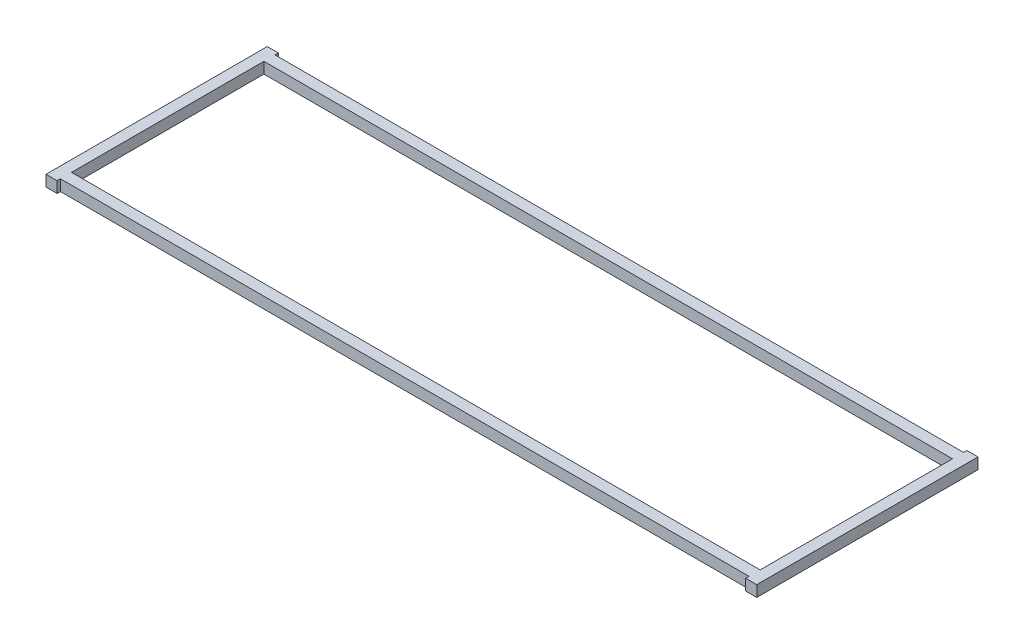
SolidWorks part; units mm, degrees
ref_plane "Front" through (0, 0, 0) normal (0, 0, 1) x (1, 0, 0)
ref_plane "Top" through (0, 0, 0) normal (0, 1, 0) x (1, 0, 0)
ref_plane "Right" through (0, 0, 0) normal (1, 0, 0) x (0, 0, -1)
sketch "Sketch1" plane through (0, 0, 0) normal (0, 1, 0) x (1, 0, 0)
  line L0 (196.85, 63.2524) -> (203.2, 63.2524)
  line L1 (-203.2, 63.2524) -> (-196.85, 63.2524)
  line L2 (-203.2, 63.2524) -> (-203.2, -63.2524)
  line L3 (-203.2, -63.2524) -> (-196.85, -63.2524)
  line L4 (203.2, 63.2524) -> (203.2, -63.2524)
  line L5 (-203.2, 63.2524) -> (203.2, -63.2524) construction
  line L6 (-203.2, -63.2524) -> (203.2, 63.2524) construction
  line L8 (-196.85, 63.2524) -> (-196.85, 61.3442)
  line L9 (-196.85, 61.3442) -> (196.85, 61.3442)
  line L10 (196.85, 63.2524) -> (196.85, 61.3442)
  line L12 (-196.85, -63.2524) -> (-196.85, -61.3442)
  line L13 (-196.85, -61.3442) -> (196.85, -61.3442)
  line L14 (196.85, -63.2524) -> (196.85, -61.3442)
  line L15 (196.85, -63.2524) -> (203.2, -63.2524)
  line L17 (-196.85, -54.9942) -> (196.85, -54.9942)
  line L18 (-196.85, -54.9942) -> (-196.85, 54.9942)
  line L19 (-196.85, 54.9942) -> (196.85, 54.9942)
  line L20 (196.85, -54.9942) -> (196.85, 54.9942)
  line L21 (-196.85, -54.9942) -> (196.85, 54.9942) construction
  line L22 (-196.85, 54.9942) -> (196.85, -54.9942) construction
  point P0 (0, 0)
  point P14 (0, 0)
  dimension "D1" = 406.4
  dimension "D2" = 126.5047
  dimension "D3" = 6.35
  dimension "D4" = 6.35
  dimension "D6" = 6.35
  dimension "D7" = 6.35
  dimension "D5" = 1.9082
extrude "Boss-Extrude1" add sketch "Sketch1" along normal blind 6.35
equation "\"D2@Sketch1\"    = (4.87075-.25) + 0.25 + ( 6 / 64 ) + 0.016"
